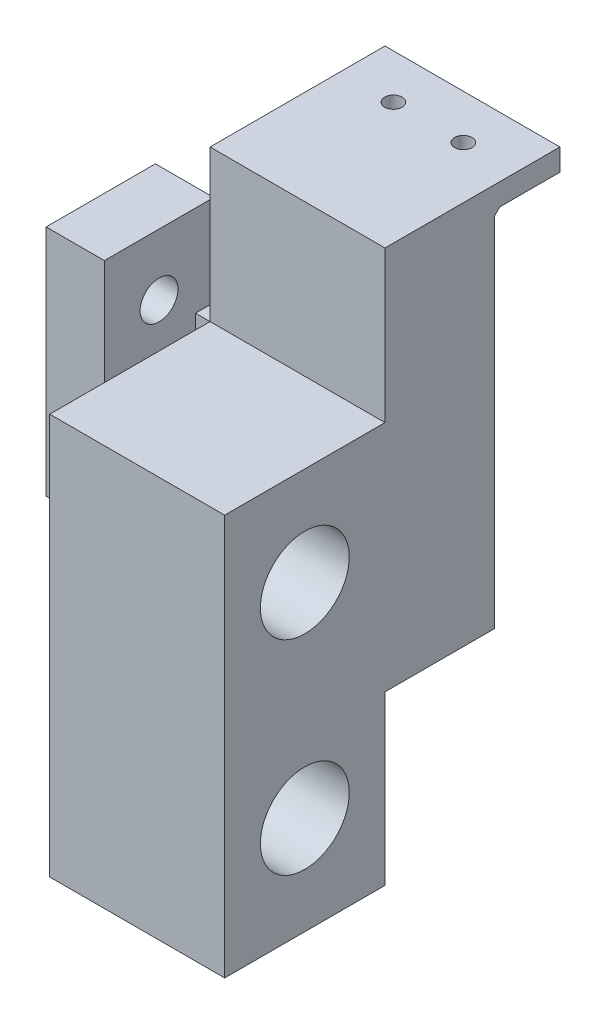
SolidWorks part; units mm, degrees
ref_plane "Front Plane" through (0, 0, 0) normal (0, 0, 1) x (1, 0, 0)
ref_plane "Top Plane" through (0, 0, 0) normal (0, 1, 0) x (1, 0, 0)
ref_plane "Right Plane" through (0, 0, 0) normal (1, 0, 0) x (0, 0, -1)
sketch "Sketch1" plane through (0, 0, 0) normal (0, 0, 1) x (1, 0, 0)
  line L8 (-49.8005, 37.5243) -> (-49.8005, -14.9757)
  line L9 (-49.8005, -14.9757) -> (-25.8005, -14.9757)
  line L10 (-25.8005, -14.9757) -> (-25.8005, 37.5243)
  line L11 (-25.8005, 37.5243) -> (-49.8005, 37.5243)
  line L13 (-37.8005, -14.9757) -> (-37.8005, -50.2864) construction
  line L14 (-41.8005, -45.2864) -> (-49.8005, -14.9757)
  line L15 (-33.8005, -45.2864) -> (-25.8005, -14.9757)
  circle A7 centre (-37.8005, -2.9757) radius 3.1
  circle A8 centre (-37.8005, 25.5243) radius 3.1
  circle A9 centre (-37.6209, 25.5243) radius 6 construction
  circle A10 centre (-37.6209, -2.9757) radius 6 construction
  circle A11 centre (-37.8005, -45.2864) radius 5 construction
  circle A12 centre (-37.8005, -45.2864) radius 2.5
  circle A13 centre (-37.8005, -45.2864) radius 7.5 construction
  circle A14 centre (-37.8005, -45.2864) radius 4
  dimension "D8" = 6.2
  dimension "D9" = 6.2
  dimension "D14" = 10
  dimension "D15" = 5
  dimension "D11" = 15
  dimension "D2" = 8
  dimension "D10" = 52.5
  dimension "D12" = 12
  dimension "D13" = 24
  dimension "D16" = 35.3107
  dimension "D17" = 24
extrude "Boss-Extrude1" add sketch "Sketch1" along normal blind 15 contours L10 L11 L8 L9 A8 A7 | A11 L15 L9 L14 | A11 A12 region at (-37.8005, 11.2743, 0) region at (-37.8005, -26.7316, 0) region at (-37.8005, -41.3996, 0)
ref_plane "Plane2" through (0, 0, 7.5) normal (0, 0, -1) x (-1, 0, 0)
sketch "Sketch5" plane through (0, 0, 7.5) normal (0, 0, -1) x (-1, 0, 0)
  circle A0 centre (37.8005, -45.2864) radius 8
extrude "Cut-Extrude2" [suppressed] cut sketch "Sketch5" against normal mid plane 7
sketch "Sketch6" plane through (0, 0, 15) normal (0, 0, 1) x (1, 0, 0)
  circle A0 centre (-37.8005, -2.9757) radius 3.1
  circle A1 centre (-37.8005, 25.5243) radius 3.1
extrude "Boss-Extrude3" add sketch "Sketch6" against normal blind 5
sketch "Sketch7" plane through (0, 0, 15) normal (0, 0, 1) x (1, 0, 0)
  line L0 (-37.8005, -50.2864) -> (-58.0505, -50.2864) construction
  line L1 (-49.8005, 16.7743) -> (-62.3005, 16.7743) construction
  line L2 (-62.3005, 16.7743) -> (-62.3005, -7.2257) construction
  line L3 (-62.3005, -7.2257) -> (-53.8005, -7.2257) construction
  line L4 (-51.8005, 16.7743) -> (-49.8005, 16.7743)
  line L5 (-53.8005, -7.2257) -> (-49.8005, -7.2257) construction
  line L6 (-58.0505, 16.7743) -> (-58.0505, -0.2257) construction
  line L7 (-58.0505, -7.2257) -> (-58.0505, -50.2864) construction
  line L8 (-49.8005, 37.5243) -> (-49.8005, -14.9757) construction
  line L9 (-58.0505, 15.2743) -> (-58.0505, 1.2743) construction
  line L10 (-51.8005, -7.2257) -> (-51.8005, 16.7743)
  line L11 (-58.0505, 8.2743) -> (-52.8005, 8.2743) construction
  line L12 (-58.0505, 8.2743) -> (-63.3005, 8.2743) construction
  line L13 (-64.3005, 16.7743) -> (-64.3005, -7.2257)
  line L14 (-64.3005, -7.2257) -> (-58.0505, -7.2257)
  line L15 (-64.3005, 16.7743) -> (-72.3005, 16.7743)
  line L16 (-72.3005, 16.7743) -> (-72.3005, -15.2257)
  line L17 (-72.3005, -15.2257) -> (-49.8005, -15.2257)
  line L18 (-58.0505, -7.2257) -> (-51.8005, -7.2257)
  line L19 (-49.8005, 16.7743) -> (-49.8005, -15.2257)
  point P17 (-58.0505, 8.2743)
  point P18 (-58.0505, 8.2743)
  dimension "D1" = 12.5
  dimension "D2" = 24
  dimension "D3" = 8
  dimension "D4" = 1
  dimension "D5" = 17
  dimension "D6" = 4
  dimension "D7" = 14
  dimension "D8" = 5.25
  dimension "D9" = 5.25
  dimension "D10" = 8
extrude "Boss-Extrude4" add sketch "Sketch7" against normal up to surface (15 mm away) up to face at (-34.7005, 25.5243, 0)
sketch "Sketch8" plane through (-72.3005, 0, 0) normal (-1, 0, 0) x (0, 0, 1)
  line L0 (7.5, 16.8468) -> (7.5, 8.3468) construction
  line L1 (7.5, 25.575) -> (7.5, -25.575) construction
  circle A0 centre (7.5, 8.3468) radius 2.6
  dimension "D1" = 5.2
extrude "Cut-Extrude3" cut sketch "Sketch8" against normal blind 27
sketch "Sketch10" plane through (0, 0, 15) normal (0, 0, 1) x (1, 0, 0)
  line L0 (-49.8005, -15.2257) -> (-49.8005, -14.9757)
  line L1 (-49.8005, -14.9757) -> (-25.8005, -14.9757)
  line L2 (-25.8005, -14.9757) -> (-25.8005, -50.6151)
  line L3 (-25.8005, -50.6151) -> (-49.8005, -50.6151)
  line L4 (-49.8005, -50.6151) -> (-49.8005, -15.2257)
extrude "Cut-Extrude4" cut sketch "Sketch10" against normal through all
sketch "Sketch11" plane through (0, 0, 15) normal (0, 0, 1) x (1, 0, 0)
  line L0 (-49.8005, -15.2257) -> (-49.8005, -14.9757)
  line L1 (-49.8005, -14.9757) -> (-25.8005, -14.9757)
  line L2 (-25.8005, -14.9757) -> (-25.8005, -15.2257)
  line L3 (-25.8005, -15.2257) -> (-49.8005, -15.2257)
extrude "Boss-Extrude5" add sketch "Sketch11" against normal up to surface (15 mm away) up to face at (-34.7005, 25.5243, 0)
sketch "Sketch12" plane through (0, 0, 15) normal (0, 0, 1) x (1, 0, 0)
  line L0 (-49.8005, 16.7743) -> (-49.8005, -38.2257)
  line L1 (-49.8005, -38.2257) -> (-25.8005, -38.2257)
  line L2 (-25.8005, -38.2257) -> (-25.8005, 16.7743)
  line L3 (-25.8005, -15.2257) -> (-25.8005, 37.5243) construction
  line L4 (-25.8005, 16.7743) -> (-49.8005, 16.7743)
  line L7 (-49.8005, -15.2257) -> (-25.8005, -15.2257)
  line L8 (-72.3005, -15.2257) -> (-25.8005, -15.2257) construction
  line M2 (-72.3005, -15.2257) -> (-25.8005, -15.2257)
  line M3 (-25.8005, -15.2257) -> (-25.8005, 37.5243)
extrude "Boss-Extrude6" add sketch "Sketch12" along normal blind 22 contours L4 L0 M3 M2 | L1 L2 L0 M2 region at (-37.8005, 0.7743, 15) region at (-37.8005, -26.7257, 15)
sketch "Sketch13" plane through (-49.8005, 0, 0) normal (-1, 0, 0) x (0, 0, 1)
  line L0 (26, 16.7743) -> (26, -38.2257) construction
  line L1 (37, 16.7743) -> (15, 16.7743) construction
  line L2 (37, -38.2257) -> (15, -38.2257) construction
  circle A0 centre (26, 3.2743) radius 6.1
  circle A1 centre (26, -24.7257) radius 6.1
  dimension "D1" = 12.2
  dimension "D2" = 12.2
  dimension "D3" = 28
extrude "Cut-Extrude5" cut sketch "Sketch13" against normal through all
sketch "Sketch14" plane through (0, 37.5243, 0) normal (0, 1, 0) x (1, 0, 0)
  line L0 (-49.8005, 0) -> (-49.8005, 9)
  line L1 (-49.8005, 9) -> (-25.8005, 9)
  line L2 (-25.8005, 9) -> (-25.8005, 0)
  circle A0 centre (-42.5505, 2.9) radius 1.2
  circle A1 centre (-32.9505, 2.9) radius 1.2
  line M2 (-25.8005, 0) -> (-49.8005, 0)
extrude "Boss-Extrude7" add sketch "Sketch14" against normal blind 3 contours L2 L1 L0 A1 A0 M2 region at (-37.8027, 37.5243, -4.57)
chamfer "Chamfer1" distance 2.5 angle 45 2 edges at (-51.8005, -7.2257, 7.5) (-64.3005, -7.2257, 7.5)
chamfer "Chamfer2" distance 0.75 angle 45 1 edges at (-37.8005, 34.5243, 0)
